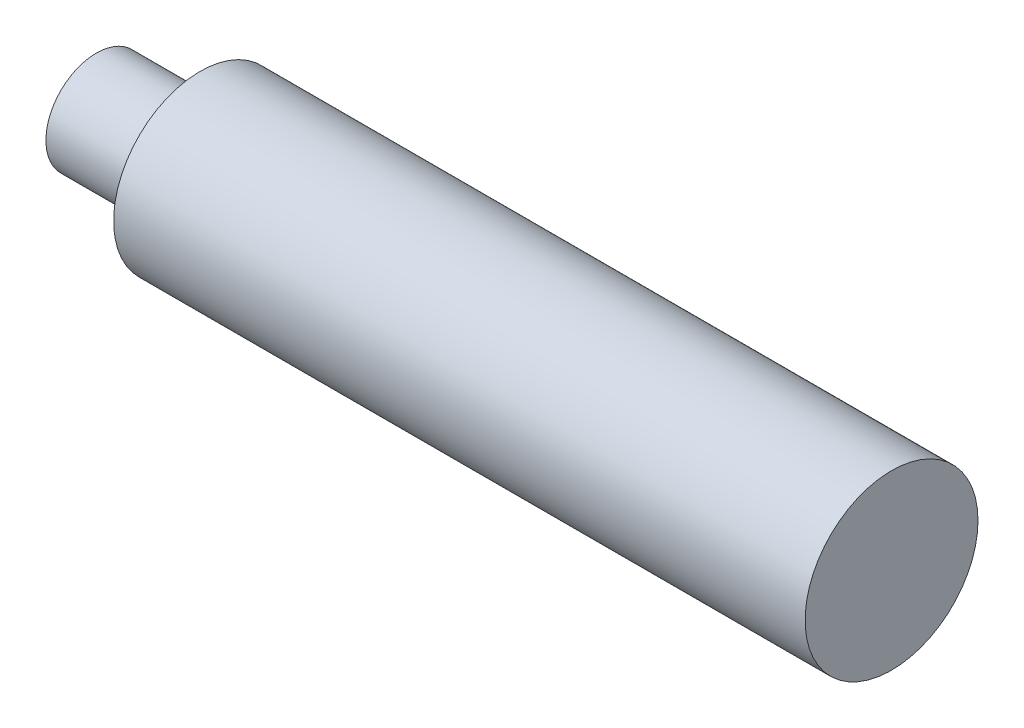
SolidWorks part; units mm, degrees
ref_plane "Front Plane" through (0, 0, 0) normal (0, 0, 1) x (1, 0, 0)
ref_plane "Top Plane" through (0, 0, 0) normal (0, 1, 0) x (1, 0, 0)
ref_plane "Right Plane" through (0, 0, 0) normal (1, 0, 0) x (0, 0, -1)
sketch "Sketch1" plane through (0, 0, 0) normal (0, 0, 1) x (1, 0, 0)
  line L0 (0, 0) -> (0, 5.5562)
  line L2 (11.43, 4.6228) -> (11.43, 9.525)
  line L3 (11.43, 9.525) -> (87.63, 9.525)
  line L4 (87.63, 9.525) -> (87.63, 0)
  line L5 (87.63, 0) -> (0, 0)
  line L6 (0, 5.5562) -> (9.525, 5.5562)
  line L7 (9.525, 5.5562) -> (9.525, 4.6228)
  line L8 (9.525, 4.6228) -> (11.43, 4.6228)
  dimension "D1" = 76.2
  dimension "D2" = 9.525
  dimension "D3" = 5.5562
  dimension "D4" = 1.905
  dimension "D5" = 9.525
  dimension "D6" = 4.6228
revolve "Torch Body" add sketch "Sketch1" angle 360 about L5
sketch "Sketch2" plane through (0, 0, 0) normal (0, 1, 0) x (1, 0, 0)
  line L0 (0, 0) -> (73.406, 0)
  line L1 (73.406, 0) -> (73.406, 2.794)
  line L2 (73.406, 2.794) -> (69.85, 6.35)
  line L3 (69.85, 6.35) -> (19.4564, 6.35)
  line L4 (19.4564, 6.35) -> (14.605, 1.4986)
  line L5 (14.605, 1.4986) -> (0, 1.4986)
  line L6 (0, 5.5562) -> (0, -5.5562) construction
  line L7 (0, 1.4986) -> (0, 0)
  line L8 (11.43, 9.525) -> (11.43, -9.525) construction
  line L10 (87.63, -9.525) -> (87.63, 9.525) construction
  point P3 (0, 0)
  dimension "D1" = 45
  dimension "D2" = 45
  dimension "D3" = 1.4986
  dimension "D4" = 6.35
  dimension "D5" = 3.175
  dimension "D6" = 2.794
  dimension "D7" = 17.78
revolve "Chamber Cavity" cut sketch "Sketch2" angle 360 about L0
fillet "Inner Chamber Fillets" radius 2.54 3 edges at (69.85, 0, 6.35) (19.4564, 0, 6.35) (14.605, 0, 1.4986)
equation "\"Torch_Length\" = 3"
equation "\"Throat_Diam\"= .118"
equation "\"H2_Orifice_Diam\" = .05"
equation "\"Film_Cooling_Orifice_Diam\"= .015"
equation "\"O2_Orifice_Diam\"= .025"
equation "\"Chamber_ID\" =0.25"
equation "\"Chamber_OD\"=0.375"
equation "\"D1@Sketch1\"=\"Torch_Length\""
equation "\"D2@Sketch1\"=\"Chamber_OD\""
equation "\"thr\"=0.101394"
equation "\"throat\"=0.101394"
equation "\"D3@Sketch2\"=\"Throat_Diam\"/2"
equation "\"D4@Sketch2\"=\"Chamber_ID\""
